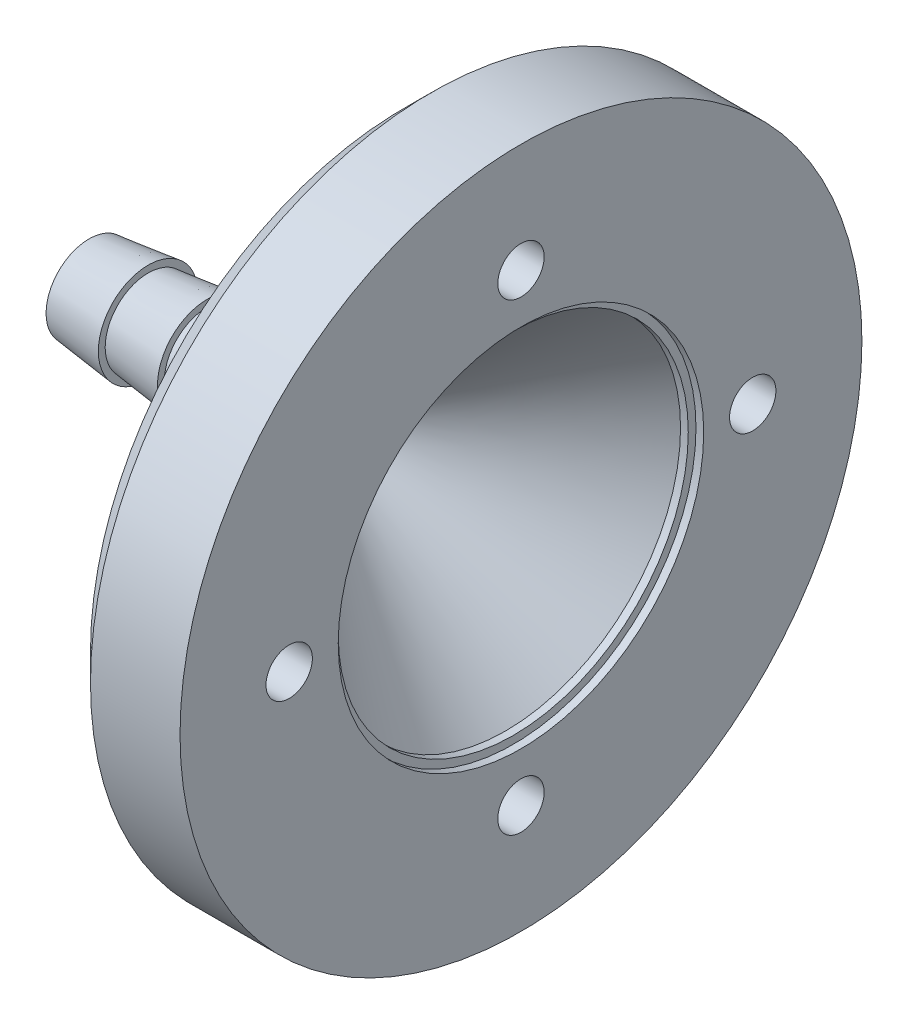
SolidWorks part; units mm, degrees
ref_plane "Front Plane" through (0, 0, 0) normal (0, 0, 1) x (1, 0, 0)
ref_plane "Top Plane" through (0, 0, 0) normal (0, 1, 0) x (1, 0, 0)
ref_plane "Right Plane" through (0, 0, 0) normal (1, 0, 0) x (0, 0, -1)
sketch "Sketch1" plane through (0, 0, 0) normal (0, 0, 1) x (1, 0, 0)
  line L0 (-801.9206, 0) -> (36107.5283, 0) construction
  line L3 (-14.1752, 3.65) -> (-14.1752, 3.15)
  line L8 (-18.5085, 1.9) -> (0, 1.9)
  line L9 (-18.5085, 1.9) -> (-18.5085, 3.15)
  line L10 (13.1623, 13.4) -> (13.1623, 25)
  line L12 (13.1623, 25) -> (4.5963, 25)
  line L16 (13.1623, 13.4) -> (12.5963, 13.4)
  line L17 (12.5963, 13.4) -> (12.5963, 12.834)
  line L18 (4.5963, 25) -> (4.5963, 12.834)
  line L20 (0, 1.9) -> (12.0303, 12.834)
  line L21 (-18.5085, 3.15) -> (-14.1752, 3.65)
  line L22 (12.0303, 12.834) -> (12.5963, 12.834)
  line L23 (-14.1752, 3.15) -> (-9.8419, 3.65)
  line L25 (-9.8419, 3.15) -> (-5.5085, 3.65)
  line L26 (-9.8419, 3.65) -> (-9.8419, 3.15)
  line L27 (-5.5085, 3.65) -> (4.5963, 12.834)
  dimension "D3" = 0.566
  dimension "D2" = 7.3
  dimension "D6" = 3.8
  dimension "D7" = 6.3
  dimension "D5" = 25
  dimension "D8" = 13.4
  dimension "D10" = 0.566
  dimension "D4" = 5
  dimension "D9" = 0.566
  dimension "D11" = 13
  dimension "D12" = 8.566
revolve "Revolve17" add sketch "Sketch1" angle 360 about L0
sketch "Sketch4" plane through (4.5963, 0, 0) normal (-1, 0, 0) x (0, 0, 1)
  circle A0 centre (0, 0) radius 16.9947 construction
  point P3 (0, 16.9947)
  point P7 (16.9947, 0)
  point P12 (-16.9947, 0)
  point P13 (0, -16.9947)
hole_wizard "CBORE for M3 Hex Socket Head Cap Screw2" positions "Sketch4" profile "Sketch5" counterbore size "M3" standard "ISO"
sketch "Sketch5" plane through (4.5963, -16.9947, 0) normal (0, 1, 0) x (0, 0, 1)
  line L0 (0, 0) -> (0, 9.5875)
  line L1 (0, 9.5875) -> (1.7, 8.566)
  line L2 (1.7, 8.566) -> (1.7, 3.4)
  line L3 (1.7, 3.4) -> (3.25, 3.4)
  line L4 (3.25, 3.4) -> (3.25, 0)
  line L5 (3.25, 0) -> (0, 0)
  line L10 (0, 9.5875) -> (-1.7, 8.566) construction
  line L11 (0, -6.35) -> (0, 107.95) construction
  dimension "Hole Dia." = 3.4
  dimension "Hole Depth" = 8.566
  dimension "C'Bore Dia." = 6.5
  dimension "C'Bore Depth" = 3.4
  dimension "Drill Angle" = 118
chamfer "Chamfer1" distance 2 angle 45 1 edges at (4.5963, 0, 25)
equation "\"D10@Sketch1\"=\"D3@Sketch1\""
equation "\"D9@Sketch1\"=\"D3@Sketch1\""
